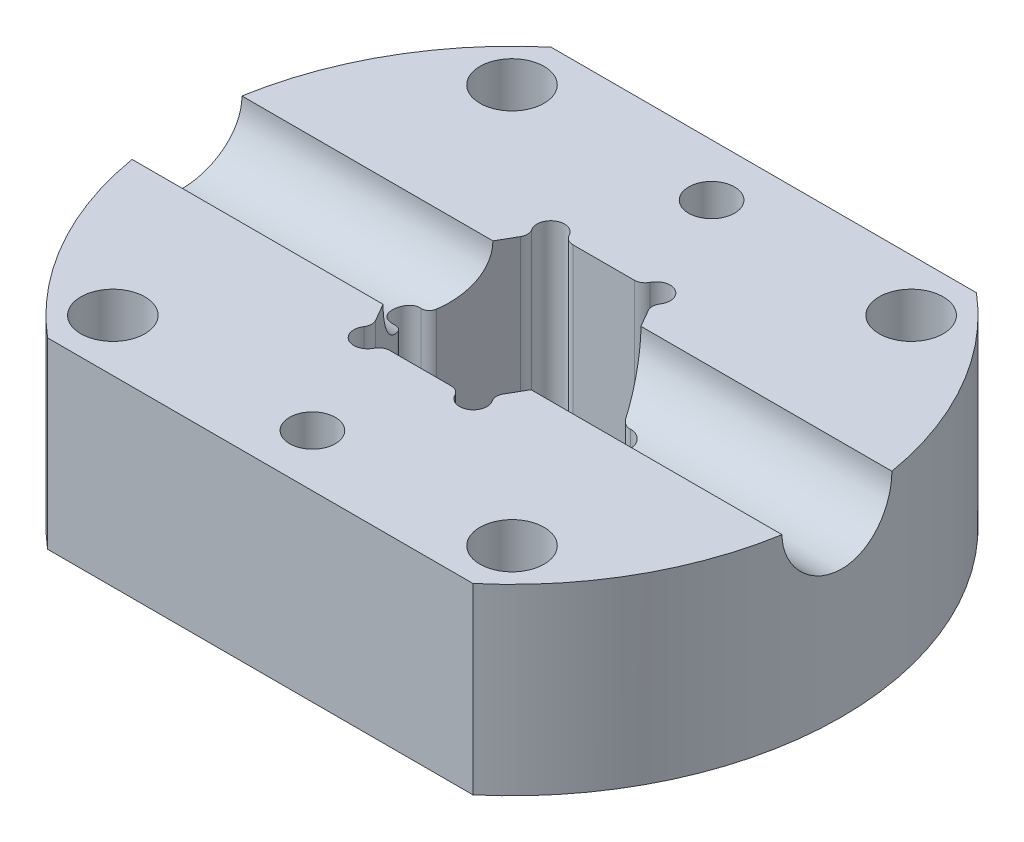
SolidWorks part; units mm, degrees
material "3.3547 (EN-AW 5083)"
ref_plane "Vorne" through (0, 0, 0) normal (0, 0, 1) x (1, 0, 0)
ref_plane "Oben" through (0, 0, 0) normal (0, 1, 0) x (1, 0, 0)
ref_plane "Rechts" through (0, 0, 0) normal (1, 0, 0) x (0, 0, -1)
sketch "Skizze1" plane through (0, 0, 0) normal (0, 1, 0) x (1, 0, 0)
  circle A0 centre (0, 0) radius 18
  dimension "D1" = 36
extrude "Aufsatz-Linear austragen1" add sketch "Skizze1" along normal blind 10
sketch "Skizze2" plane through (0, 10, 0) normal (0, 1, 0) x (1, 0, 0)
  line L1 (-18, -13.75) -> (18, -13.75)
  line L2 (-18, -13.75) -> (-18, 13.75)
  line L3 (-18, 13.75) -> (18, 13.75)
  line L4 (18, -13.75) -> (18, 13.75)
  line L5 (-18, -13.75) -> (18, 13.75) construction
  line L6 (-18, 13.75) -> (18, -13.75) construction
  circle A0 centre (0, 0) radius 18 construction
  point P0 (0, 0)
  dimension "D1" = 27.5
extrude "Schnitt-Linear austragen1" cut sketch "Skizze2" against normal blind 10 flip side to cut
sketch "Skizze3" plane through (0, 10, 0) normal (0, 1, 0) x (1, 0, 0)
  line L1 (2.8868, 5) -> (-2.8868, 5)
  line L2 (-2.8868, 5) -> (-5.7735, 0)
  line L3 (-5.7735, 0) -> (-2.8868, -5)
  line L4 (-2.8868, -5) -> (2.8868, -5)
  line L5 (2.8868, -5) -> (5.7735, 0)
  line L6 (5.7735, 0) -> (2.8868, 5)
  line L8 (-2.8448, 0) -> (2.8448, 0) construction
  circle A0 centre (0, 0) radius 5 construction
  dimension "D1" = 10
extrude "Schnitt-Linear austragen2" cut sketch "Skizze3" against normal blind 10
sketch "Skizze4" plane through (0, 0, 0) normal (1, 0, 0) x (0, 0, -1)
  line L0 (13.75, 10) -> (-13.75, 10) construction
  circle A0 centre (0, 10) radius 3
  dimension "D1" = 6
extrude "Schnitt-Linear austragen3" cut sketch "Skizze4" against normal mid plane 45
hole_wizard "M3 Gewindebohrung1" positions "Skizze5" profile "Skizze6" tap size "M3" standard "DIN" end condition through all
sketch "Skizze5" plane through (0, 10, 0) normal (0, 1, 0) x (1, 0, 0)
  line L0 (0, -2.75) -> (0, 2.75) construction
  line L1 (-5.5, 0) -> (5.5, 0) construction
  point P0 (0, 10.9)
  point P4 (0, -10.9)
  dimension "D1" = 10.9
  dimension "D2" = 21.8
sketch "Skizze6" plane through (0, 10, -10.9) normal (1, 0, 0) x (0, 0, 1)
  line L0 (0, 0) -> (0, 10)
  line L1 (0, 10) -> (1.25, 10)
  line L2 (1.25, 10) -> (1.25, 0)
  line L5 (1.25, 0) -> (0, 0)
  line L11 (0, -6.35) -> (0, 107.95) construction
  dimension "Bohrerdurchmesser" = 2.5
  dimension "Bohrungstiefe" = 10
cosmetic thread "Bohrungsgewinde1" parameters "D2"=3
cosmetic thread "Bohrungsgewinde2" parameters "D2"=3
hole_wizard "Ø3.5 (3.5) Durchmesser Bohrung1" positions "Skizze7" profile "Skizze8" hole size "Ø3.5" standard "DIN" end condition through all
sketch "Skizze7" plane through (0, 10, 0) normal (0, 1, 0) x (1, 0, 0)
  line L0 (-5.5, 0) -> (5.5, 0) construction
  line L1 (0, -2.75) -> (0, 2.75) construction
  point P0 (-10.9, 10.9)
  point P2 (10.9, 10.9)
  point P4 (10.9, -10.9)
  point P6 (-10.9, -10.9)
  dimension "D1" = 10.9
  dimension "D2" = 10.9
  dimension "D3" = 21.8
  dimension "D4" = 21.8
sketch "Skizze8" plane through (-10.9, 10, -10.9) normal (1, 0, 0) x (0, 0, 1)
  line L0 (0, 0) -> (0, 10)
  line L1 (0, 10) -> (1.75, 10)
  line L2 (1.75, 10) -> (1.75, 0)
  line L5 (1.75, 0) -> (0, 0)
  line L11 (0, -6.35) -> (0, 107.95) construction
  dimension "Bohrerdurchmesser" = 3.5
  dimension "Bohrungstiefe" = 10
sketch "Skizze9" plane through (0, 10, 0) normal (0, 1, 0) x (1, 0, 0)
  circle A0 centre (-2.8868, 5) radius 0.75
  circle A1 centre (2.8868, 5) radius 0.75
  circle A2 centre (5.7735, 0) radius 0.75
  circle A3 centre (2.8868, -5) radius 0.75
  circle A4 centre (-2.8868, -5) radius 0.75
  circle A5 centre (-5.7735, 0) radius 0.75
  dimension "D1" = 1.5
extrude "Schnitt-Linear austragen4" cut sketch "Skizze9" against normal blind 10
fillet "Verrundung1" radius 0.6 12 edges at (5.3985, 3.5356, -0.6495) (5.3985, 3.5356, 0.6495) (3.2618, 5, 4.3505) (2.1368, 5, 5) (-2.1368, 5, 5) (-3.2618, 5, 4.3505) (-5.3985, 3.5356, 0.6495) (-5.3985, 3.5356, -0.6495) (-3.2618, 5, -4.3505) (-2.1368, 5, -5) (2.1368, 5, -5) (3.2618, 5, -4.3505)
